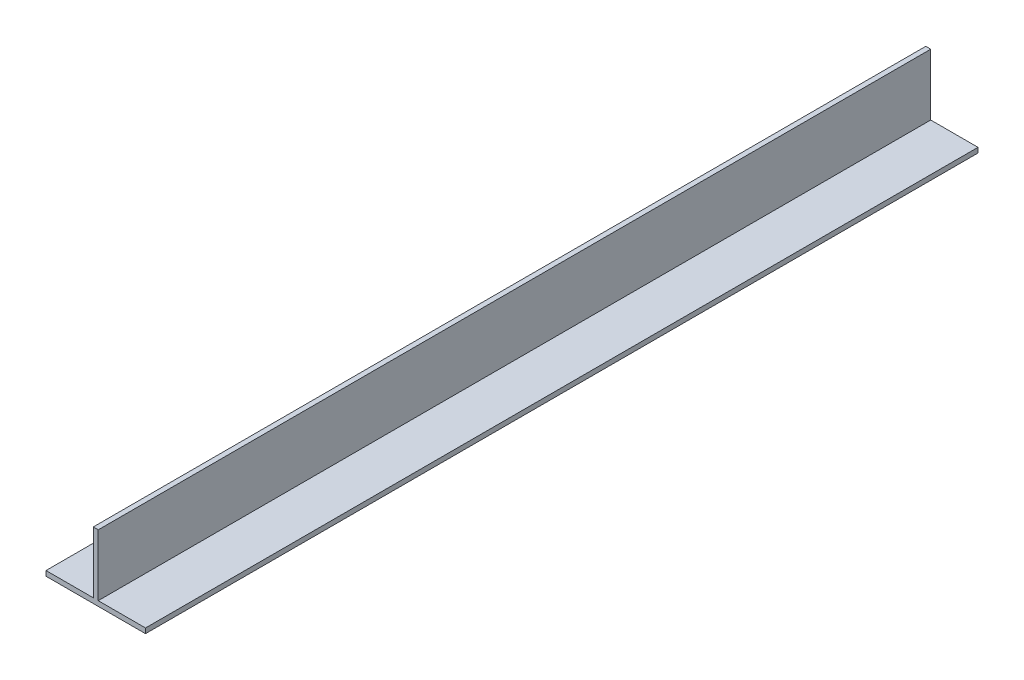
SolidWorks part; units mm, degrees
material "1060 Сплав"
ref_plane "Спереди" through (0, 0, 0) normal (0, 0, 1) x (1, 0, 0)
ref_plane "Сверху" through (0, 0, 0) normal (0, 1, 0) x (1, 0, 0)
ref_plane "Справа" through (0, 0, 0) normal (1, 0, 0) x (0, 0, -1)
sketch "Эскиз1" plane through (0, 0, 0) normal (0, 0, 1) x (1, 0, 0)
  line L0 (0, 0) -> (0, 18.5)
  line L1 (0, 18.5) -> (1.5, 18.5)
  line L2 (1.5, 18.5) -> (1.5, 0)
  line L3 (1.5, 0) -> (15.75, 0)
  line L4 (15.75, 0) -> (15.75, -1.5)
  line L5 (15.75, -1.5) -> (-14.25, -1.5)
  line L6 (-14.25, -1.5) -> (-14.25, 0)
  line L7 (-14.25, 0) -> (0, 0)
  dimension "D1" = 30
  dimension "D2" = 20
  dimension "D3" = 1.5
extrude "Бобышка-Вытянуть1" add sketch "Эскиз1" along normal blind 251
